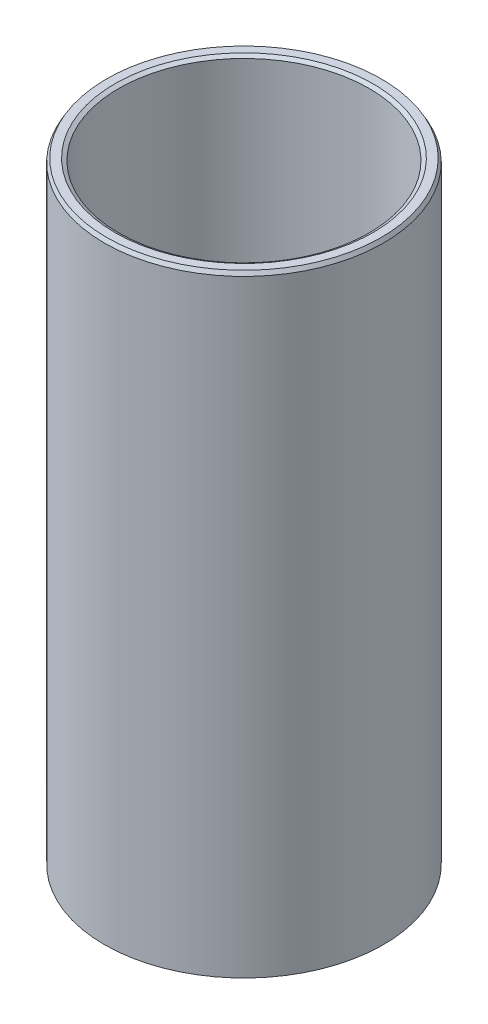
SolidWorks part; units mm, degrees
ref_plane "Front Plane" through (0, 0, 0) normal (0, 0, 1) x (1, 0, 0)
ref_plane "Top Plane" through (0, 0, 0) normal (0, 1, 0) x (1, 0, 0)
ref_plane "Right Plane" through (0, 0, 0) normal (1, 0, 0) x (0, 0, -1)
sketch "Sketch1" plane through (0, 0, 0) normal (0, 1, 0) x (1, 0, 0)
  circle A0 centre (0, 0) radius 50
  dimension "SLEEVE_OD" = 100
extrude "Boss-Extrude1" add sketch "Sketch1" along normal blind 219.8637
sketch "Sketch2" plane through (0, 0, 0) normal (0, 1, 0) x (1, 0, 0)
  circle A0 centre (0, 0) radius 44.8653
  dimension "BORE_D" = 89.7305
extrude "Cut-Extrude1" cut sketch "Sketch2" along normal through all
chamfer "Chamfer1" distance 1.3559 angle 30 4 edges at (0, 219.8637, 44.8653) (0, 0, 44.8653) (0, 0, 50) (0, 219.8637, 50) first distance on face at (0, 219.8637, 44.8653) first distance on face at (0, 0, 44.8653) first distance on face at (0, 219.8637, 50)
